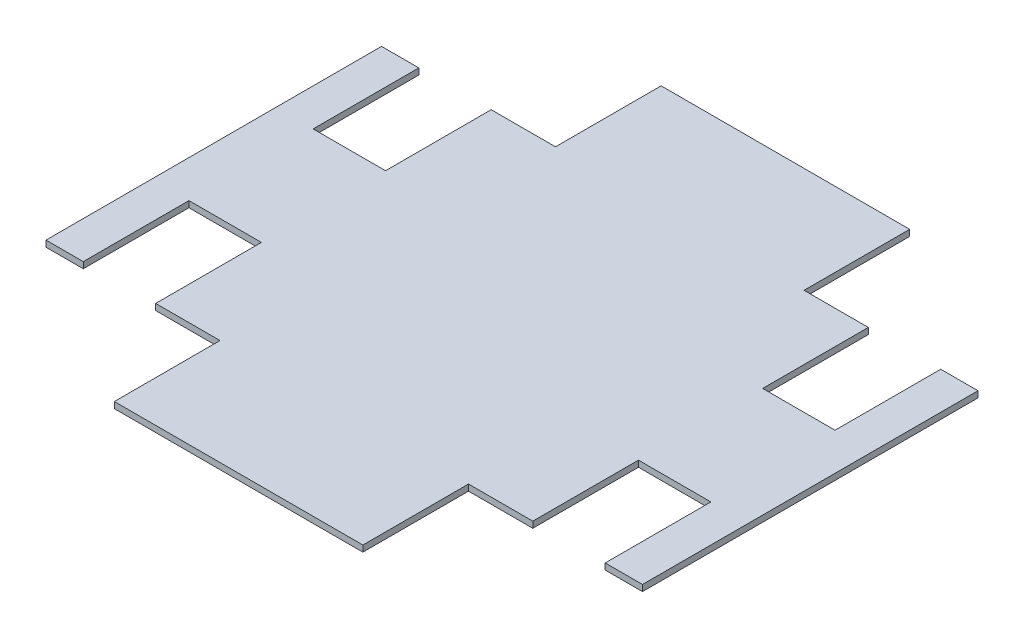
SolidWorks part; units mm, degrees
ref_plane "Front Plane" through (0, 0, 0) normal (0, 0, 1) x (1, 0, 0)
ref_plane "Top Plane" through (0, 0, 0) normal (0, 1, 0) x (1, 0, 0)
ref_plane "Right Plane" through (0, 0, 0) normal (1, 0, 0) x (0, 0, -1)
sketch "Sketch1" plane through (0, 0, 0) normal (0, 1, 0) x (1, 0, 0)
  line L0 (152.4, 85.725) -> (63.5, 85.725)
  line L1 (-152.4, -139.7) -> (152.4, -139.7)
  line L2 (-152.4, -139.7) -> (-152.4, 139.7)
  line L3 (-152.4, 139.7) -> (152.4, 139.7)
  line L4 (152.4, -139.7) -> (152.4, 139.7)
  line L5 (-152.4, -139.7) -> (152.4, 139.7) construction
  line L6 (-152.4, 139.7) -> (152.4, -139.7) construction
  line L7 (63.5, 85.725) -> (63.5, 139.7)
  line L8 (-152.4, 85.725) -> (-63.5, 85.725)
  line L9 (-63.5, 85.725) -> (-63.5, 139.7)
  line L10 (-152.4, -85.725) -> (-63.5, -85.725)
  line L11 (-63.5, -85.725) -> (-63.5, -139.7)
  line L12 (152.4, -85.725) -> (63.5, -85.725)
  line L13 (63.5, -85.725) -> (63.5, -139.7)
  line L14 (-96.35, 31.725) -> (96.35, 31.725) construction
  line L15 (96.35, 31.725) -> (133.35, 31.725)
  line L16 (96.35, 31.725) -> (96.35, 85.725)
  line L17 (96.35, 85.725) -> (133.35, 85.725)
  line L18 (133.35, 31.725) -> (133.35, 85.725)
  line L19 (96.35, 31.725) -> (133.35, 85.725) construction
  line L20 (96.35, 85.725) -> (133.35, 31.725) construction
  line L21 (96.35, -31.725) -> (133.35, -31.725)
  line L22 (96.35, -31.725) -> (96.35, -85.725)
  line L23 (96.35, -85.725) -> (133.35, -85.725)
  line L24 (133.35, -31.725) -> (133.35, -85.725)
  line L25 (96.35, -31.725) -> (133.35, -85.725) construction
  line L26 (96.35, -85.725) -> (133.35, -31.725) construction
  line L27 (-133.35, -31.725) -> (-96.35, -31.725)
  line L28 (-133.35, -31.725) -> (-133.35, -85.725)
  line L29 (-133.35, -85.725) -> (-96.35, -85.725)
  line L30 (-96.35, -31.725) -> (-96.35, -85.725)
  line L31 (-133.35, -31.725) -> (-96.35, -85.725) construction
  line L32 (-133.35, -85.725) -> (-96.35, -31.725) construction
  line L33 (-133.35, 31.725) -> (-96.35, 31.725)
  line L34 (-133.35, 31.725) -> (-133.35, 85.725)
  line L35 (-133.35, 85.725) -> (-96.35, 85.725)
  line L36 (-96.35, 31.725) -> (-96.35, 85.725)
  line L37 (-133.35, 31.725) -> (-96.35, 85.725) construction
  line L38 (-133.35, 85.725) -> (-96.35, 31.725) construction
  point P0 (0, 0)
  point P18 (114.85, 58.725)
  point P23 (114.85, -58.725)
  point P28 (-114.85, -58.725)
  point P33 (-114.85, 58.725)
  point P38 (0, 31.725)
  dimension "D1" = 304.8
  dimension "D2" = 279.4
  dimension "D3" = 53.975
  dimension "D4" = 88.9
  dimension "D5" = 54
  dimension "D6" = 37
  dimension "D7" = 19.05
extrude "Boss-Extrude1" add sketch "Sketch1" along normal blind 3.175 contours L13 L12 L4 L0 L7 L3 L9 L8 L2 L10 L11 L1 region at (0, 0, 0)
